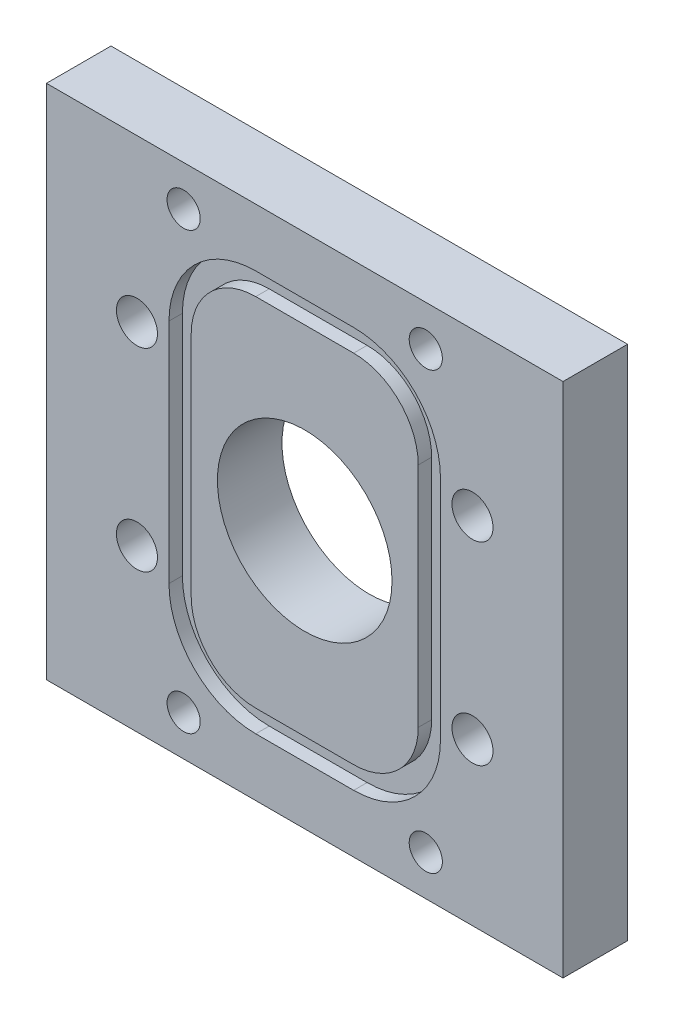
SolidWorks part; units mm, degrees
material "6061 Alloy"
ref_plane "Front Plane" through (0, 0, 0) normal (0, 0, 1) x (1, 0, 0)
ref_plane "Top Plane" through (0, 0, 0) normal (0, 1, 0) x (1, 0, 0)
ref_plane "Right Plane" through (0, 0, 0) normal (1, 0, 0) x (0, 0, -1)
sketch "Sketch1" plane through (0, 0, 0) normal (0, 0, 1) x (1, 0, 0)
  line L1 (-25.4, -25.4) -> (25.4, -25.4)
  line L2 (-25.4, -25.4) -> (-25.4, 25.4)
  line L3 (-25.4, 25.4) -> (25.4, 25.4)
  line L4 (25.4, -25.4) -> (25.4, 25.4)
  line L5 (-25.4, -25.4) -> (25.4, 25.4) construction
  line L6 (-25.4, 25.4) -> (25.4, -25.4) construction
  point P0 (0, 0)
  dimension "D1" = 50.8
  dimension "D2" = 50.8
extrude "Boss-Extrude1" add sketch "Sketch1" along normal blind 6.35
sketch "Sketch2" plane through (0, 0, 6.35) normal (0, 0, 1) x (1, 0, 0)
  line L0 (-4.7625, -15.875) -> (4.7625, -15.875) construction
  line L1 (-9.525, -11.1125) -> (-9.525, 11.1125) construction
  line L2 (-4.7625, 15.875) -> (4.7625, 15.875) construction
  line L3 (9.525, -11.1125) -> (9.525, 11.1125) construction
  line L4 (-9.525, -15.875) -> (9.525, 15.875) construction
  line L5 (-9.525, 15.875) -> (9.525, -15.875) construction
  line L6 (25.4, 25.4) -> (-25.4, 25.4) construction
  line L7 (-25.4, 25.4) -> (-25.4, -25.4) construction
  arc A0 (-4.7625, -15.875) -> (-9.525, -11.1125) centre (-4.7625, -11.1125) cw construction
  arc A1 (4.7625, -15.875) -> (9.525, -11.1125) centre (4.7625, -11.1125) ccw construction
  arc A2 (4.7625, 15.875) -> (9.525, 11.1125) centre (4.7625, 11.1125) cw construction
  arc A3 (-9.525, 11.1125) -> (-4.7625, 15.875) centre (-4.7625, 11.1125) cw construction
  circle A4 centre (0, 0) radius 8.5852
  point P0 (0, 0)
  point P19 (0, 25.4)
  point P22 (-25.4, 0)
  dimension "D2" = 4.7625
  dimension "D4" = 17.1704
  dimension "D1" = 31.75
  dimension "D3" = 19.05
extrude "Cut-Extrude1" cut sketch "Sketch2" against normal through all
sketch "Sketch3" plane through (0, 0, 6.35) normal (0, 0, 1) x (1, 0, 0)
  line L0 (13.3477, -11.176) -> (13.3477, 11.176)
  line L1 (-4.8133, -17.526) -> (4.8133, -17.526)
  line L2 (-11.1633, -11.176) -> (-11.1633, 11.176)
  line L3 (-4.8133, 17.526) -> (4.8133, 17.526)
  line L4 (11.1633, -11.176) -> (11.1633, 11.176)
  line L5 (-11.1633, -17.526) -> (11.1633, 17.526) construction
  line L6 (-11.1633, 17.526) -> (11.1633, -17.526) construction
  line L7 (-4.8133, -19.7104) -> (4.8133, -19.7104)
  line L8 (-13.3477, -11.176) -> (-13.3477, 11.176)
  line L9 (-4.8133, 19.7104) -> (4.8133, 19.7104)
  arc A0 (-4.8133, -17.526) -> (-11.1633, -11.176) centre (-4.8133, -11.176) cw
  arc A1 (4.8133, -17.526) -> (11.1633, -11.176) centre (4.8133, -11.176) ccw
  arc A2 (4.8133, 17.526) -> (11.1633, 11.176) centre (4.8133, 11.176) cw
  arc A3 (-11.1633, 11.176) -> (-4.8133, 17.526) centre (-4.8133, 11.176) cw
  arc A4 (4.8133, 19.7104) -> (13.3477, 11.176) centre (4.8133, 11.176) cw
  arc A5 (4.8133, -19.7104) -> (13.3477, -11.176) centre (4.8133, -11.176) ccw
  arc A6 (-4.8133, -19.7104) -> (-13.3477, -11.176) centre (-4.8133, -11.176) cw
  arc A7 (-13.3477, 11.176) -> (-4.8133, 19.7104) centre (-4.8133, 11.176) cw
  point P0 (0, 0)
  dimension "D1" = 6.35
  dimension "D2" = 9.6266
  dimension "D3" = 22.352
  dimension "D4" = 2.1844
extrude "Cut-Extrude2 - dash 027" cut sketch "Sketch3" against normal blind 1.3208
hole_wizard "CSK for #4 Flat Head Machine Screw (100)1" positions "Sketch7" profile "Sketch6" countersink size "#4" standard "Ansi Inch" end condition through all
sketch "Sketch7" plane through (0, 0, 0) normal (0, 0, -1) x (-1, 0, 0)
  line L0 (-25.4, 25.4) -> (25.4, 25.4) construction
  line L1 (25.4, -25.4) -> (-25.4, -25.4) construction
  line L2 (25.4, 25.4) -> (25.4, -25.4) construction
  line L3 (-25.4, -25.4) -> (-25.4, 25.4) construction
  point P0 (-11.9062, 21.4312)
  point P1 (11.9062, 21.4312)
  point P3 (-11.9062, -21.4313)
  point P5 (11.9062, -21.4313)
  dimension "D1" = 3.9688
  dimension "D2" = 3.9688
  dimension "D3" = 13.4937
  dimension "D4" = 13.4937
sketch "Sketch6" plane through (11.9062, 21.4312, 0) normal (1, 0, 0) x (0, 1, 0)
  line L0 (0, 0) -> (0, 6.35)
  line L1 (0, 6.35) -> (1.6319, 6.35)
  line L2 (1.6319, 6.35) -> (1.6319, 1.0284)
  line L3 (1.6319, 1.0284) -> (2.8575, 0)
  line L5 (2.8575, 0) -> (0, 0)
  line L6 (-1.6319, 1.0284) -> (-2.8575, 0) construction
  line L11 (0, -6.35) -> (0, 107.95) construction
  dimension "Thru Hole Dia." = 3.2639
  dimension "Thru Hole Depth" = 6.35
  dimension "Near C'Sink Dia." = 5.715
  dimension "Near C'Sink Angle" = 100
ref_plane "Plane1" through (0, 0, 3.175) normal (0, 0, -1) x (-1, 0, 0)
hole_wizard "#10-32 Tapped Hole1" positions "Sketch9" profile "Sketch8" tap size "#10-32" standard "Ansi Inch"
sketch "Sketch9" plane through (0, 0, 0) normal (0, 0, -1) x (-1, 0, 0)
  line L1 (0, 26.7758) -> (0, -27.9095) construction
  line L4 (-26.8425, 0) -> (28.1096, 0) construction
  line L7 (-33.2746, -19.2111) -> (33.2649, 19.2055) construction
  line L10 (-29.1442, 16.8264) -> (35.88, -20.7153) construction
  point P21 (16.4978, 9.525)
  point P34 (16.4978, -9.525)
  dimension "D1" = 30
  dimension "D2" = 19.05
  dimension "D3" = 30
sketch "Sketch8" plane through (-16.4978, 9.525, 0) normal (1, 0, 0) x (0, 1, 0)
  line L0 (0, 0) -> (0, 14.9293)
  line L1 (0, 14.9293) -> (2.0193, 13.716)
  line L2 (2.0193, 13.716) -> (2.0193, 0)
  line L5 (2.0193, 0) -> (0, 0)
  line L10 (0, 14.9293) -> (-2.0193, 13.716) construction
  line L11 (0, -6.35) -> (0, 107.95) construction
  dimension "Tap Drill Dia." = 4.0386
  dimension "Tap Drill Depth" = 13.716
  dimension "Drill Angle" = 118
mirror "Mirror1" about plane through (0, 0, 0) normal (1, 0, 0) of "#10-32 Tapped Hole1"
